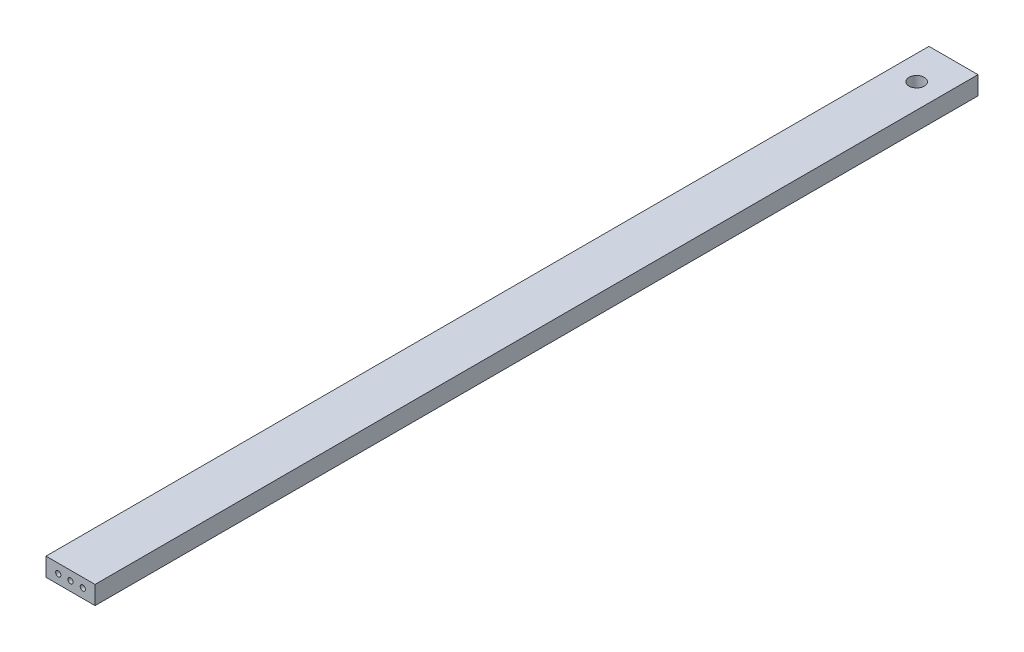
SolidWorks part; units mm, degrees
material "6061-T6 (SS)"
ref_plane "Front Plane" through (0, 0, 0) normal (0, 0, 1) x (1, 0, 0)
ref_plane "Top Plane" through (0, 0, 0) normal (0, 1, 0) x (1, 0, 0)
ref_plane "Right Plane" through (0, 0, 0) normal (1, 0, 0) x (0, 0, -1)
other "Configuration Table"
sketch "Sketch1" plane through (0, 0, 0) normal (0, 1, 0) x (1, 0, 0)
  line L1 (-12.7, 19.05) -> (12.7, 19.05)
  line L2 (-12.7, 19.05) -> (-12.7, -438.15)
  line L3 (-12.7, -438.15) -> (12.7, -438.15)
  line L4 (12.7, 19.05) -> (12.7, -438.15)
  circle A0 centre (0, 0) radius 3.9688
  point P12 (0, 19.05)
  point P17 (0, 0)
  point P18 (0, 0)
  point P19 (0, 0)
  point P20 (0, 0)
  point P21 (-7.2972, 2.973)
  dimension "D4" = 7.9375
  dimension "D1" = 19.05
  dimension "D2" = 457.2
  dimension "D3" = 25.4
extrude "Boss-Extrude1" add sketch "Sketch1" along normal blind 9.525 separate body
sketch "Sketch6" plane through (0, 0, 438.15) normal (0, 0, 1) x (1, 0, 0)
  line L0 (-12.7, 4.7625) -> (-6.35, 4.7625) construction
  line L5 (-12.7, 9.525) -> (-12.7, 0) construction
  line L8 (-6.35, 4.7625) -> (0, 4.7625) construction
  line L9 (0, 4.7625) -> (6.35, 4.7625) construction
  line L10 (6.35, 4.7625) -> (12.7, 4.7625) construction
  line L11 (12.7, 9.525) -> (12.7, 0) construction
  point P1 (-6.35, 4.7625)
  point P5 (0, 4.7625)
  point P6 (6.35, 4.7625)
sketch "Sketch8" plane through (0, 0, 438.15) normal (0, 0, 1) x (1, 0, 0)
  point P0 (-6.35, 4.7625)
  point P3 (0, 4.7625)
  point P6 (6.35, 4.7625)
hole_wizard "#6-32 Tapped Hole2" positions "Sketch8" profile "Sketch9" tap size "#6-32" standard "ANSI Inch"
cosmetic thread "Hole Thread1" parameters "D1"=9.525, "D2"=3.5052
cosmetic thread "Hole Thread2" parameters "D1"=9.525, "D2"=3.5052
cosmetic thread "Hole Thread3" parameters "D1"=9.525, "D2"=3.5052
sketch "Sketch9" plane through (-6.35, 4.7625, 438.15) normal (1, 0, 0) x (0, -1, 0)
  line L0 (0, 0) -> (0, 14.3001)
  line L1 (0, 14.3001) -> (1.3525, 13.4874)
  line L2 (1.3525, 13.4874) -> (1.3525, 0)
  line L5 (1.3525, 0) -> (0, 0)
  line L10 (0, 14.3001) -> (-1.3525, 13.4874) construction
  line L11 (0, -6.35) -> (0, 107.95) construction
  dimension "Tap Drill Dia." = 2.7051
  dimension "Tap Drill Depth" = 13.4874
  dimension "Drill Angle" = 118
